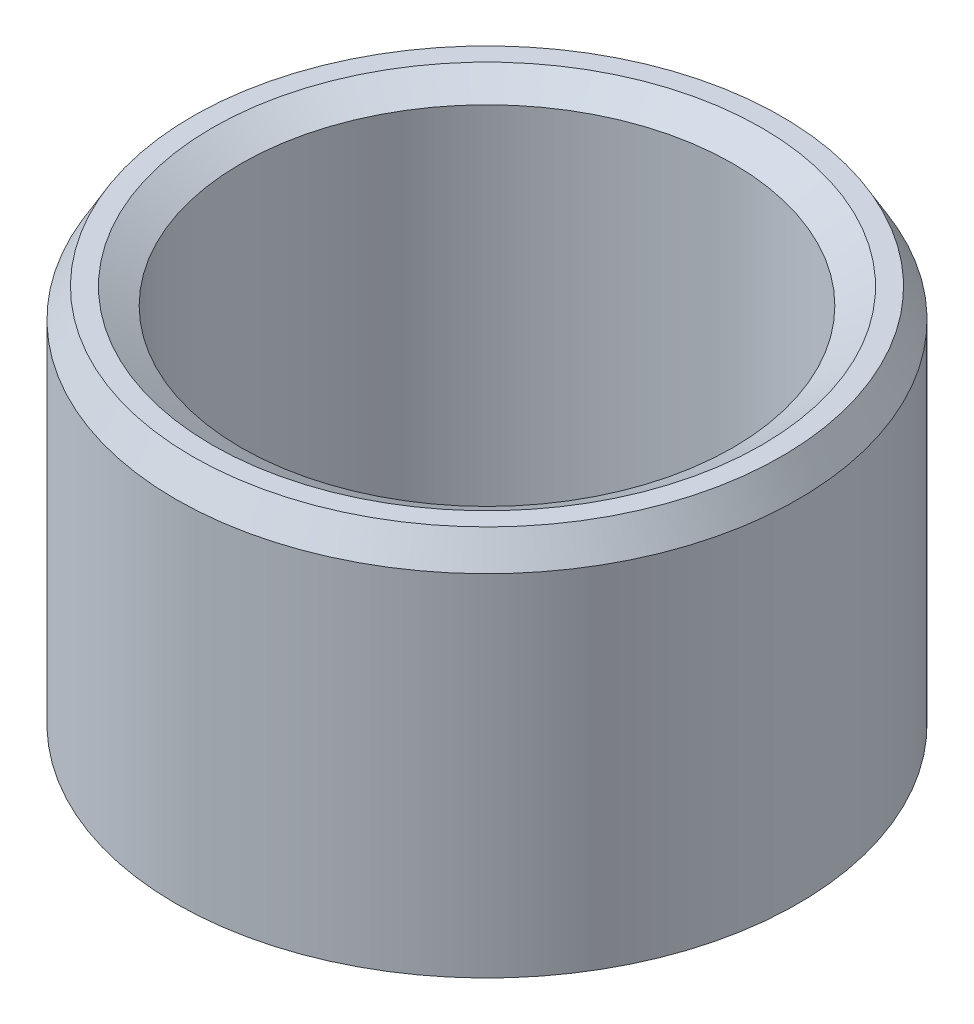
SolidWorks part; units mm, degrees
ref_plane "Front Plane" through (0, 0, 0) normal (0, 0, 1) x (1, 0, 0)
ref_plane "Top Plane" through (0, 0, 0) normal (0, 1, 0) x (1, 0, 0)
ref_plane "Right Plane" through (0, 0, 0) normal (1, 0, 0) x (0, 0, -1)
sketch "Sketch1" plane through (0, 0, 0) normal (0, 1, 0) x (1, 0, 0)
  circle A0 centre (0, 0) radius 25
  dimension "SLEEVE_OD" = 50
extrude "Boss-Extrude1" add sketch "Sketch1" along normal blind 31.7757
sketch "Sketch2" plane through (0, 0, 0) normal (0, 1, 0) x (1, 0, 0)
  circle A0 centre (0, 0) radius 19.7615
  dimension "BORE_D" = 39.5229
extrude "Cut-Extrude1" cut sketch "Sketch2" along normal through all
chamfer "Chamfer1" distance 2.312 angle 30 4 edges at (0, 31.7757, 19.7615) (0, 0, 19.7615) (0, 0, 25) (0, 31.7757, 25) first distance on face at (0, 31.7757, 19.7615) first distance on face at (0, 0, 19.7615) first distance on face at (0, 31.7757, 25)
